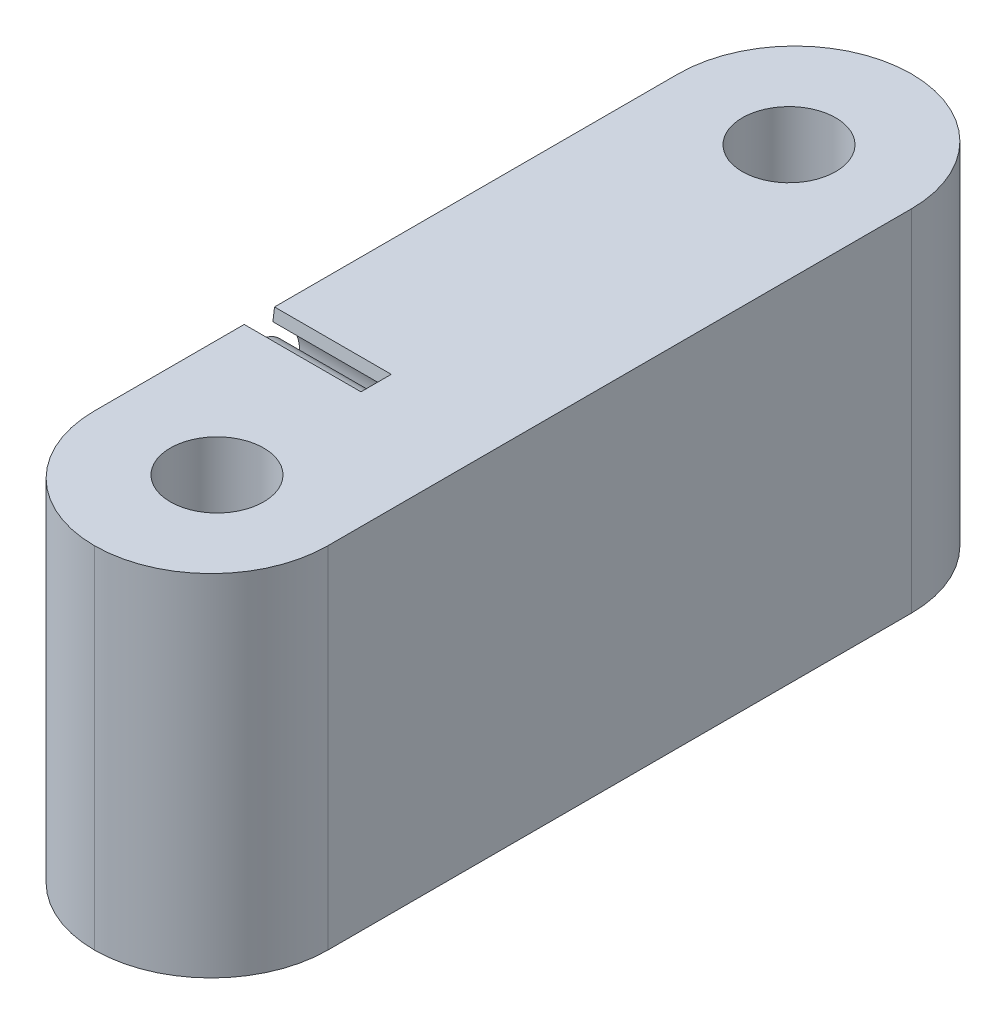
SolidWorks part; units mm, degrees
ref_plane "Front Plane" through (0, 0, 0) normal (0, 0, 1) x (1, 0, 0)
ref_plane "Top Plane" through (0, 0, 0) normal (0, 1, 0) x (1, 0, 0)
ref_plane "Right Plane" through (0, 0, 0) normal (1, 0, 0) x (0, 0, -1)
sketch "Sketch2" plane through (0, 0, 0) normal (0, 1, 0) x (1, 0, 0)
  line L1 (-3.5224, 29.7612) -> (16.4776, 29.7612)
  line L2 (-3.5224, 29.7612) -> (-3.5224, -40.2388)
  line L3 (-3.5224, -40.2388) -> (16.4776, -40.2388)
  line L4 (16.4776, 29.7612) -> (16.4776, -40.2388)
  dimension "D1" = 70
  dimension "D2" = 20
extrude "Boss-Extrude1" add sketch "Sketch2" along normal blind 30
sketch "Sketch3" plane through (0, 30, 0) normal (0, 1, 0) x (1, 0, 0)
  line L1 (-3.5224, -40.2388) -> (16.4776, -40.2388) construction
  line L3 (16.4776, -40.2388) -> (16.4776, 29.7612) construction
  line L4 (16.4776, 29.7612) -> (-3.5224, 29.7612) construction
  circle A0 centre (6.4776, 19.2612) radius 4
  circle A1 centre (6.4776, -29.7388) radius 4
  point P2 (0, 0)
  point P7 (0, 0)
  point P9 (-83.4642, 48.7576)
  dimension "D13" = 8
  dimension "D14" = 8
  dimension "D2" = 49
  dimension "D3" = 10.5
  dimension "D4" = 10.5
  dimension "D5" = 10
extrude "Cut-Extrude1" cut sketch "Sketch3" against normal blind 20
sketch "Sketch4" plane through (-3.5224, 0, 0) normal (-1, 0, 0) x (0, 0, 1)
  line L0 (8.1636, 30.0512) -> (8.1636, 15.6029) construction
  line L1 (-23.743, 30.1264) -> (40.1453, 30.1264)
  line L2 (-23.743, 30.1264) -> (-23.743, 15.6782)
  line L3 (-23.743, 15.6782) -> (40.1453, 15.6782)
  line L4 (40.1453, 30.1264) -> (40.1453, 15.6782)
  line L5 (14.95, 28.9694) -> (14.7857, 30.2017)
  line L6 (14.7857, 30.2017) -> (17.4195, 30.2017)
  line L7 (17.4195, 30.2017) -> (17.3442, 28.9224)
  circle A0 centre (16.1636, 25.6866) radius 2.5
  circle A1 centre (16.1636, 25.6866) radius 3.5
  line M5 (40.2388, 30) -> (-29.7612, 30)
  dimension "D2" = 5
  dimension "D3" = 7
  dimension "D1" = 8
extrude "Cut-Extrude2" cut sketch "Sketch4" against normal blind 10 contours A1 L7 L5 M5 | A1 A0 region at (-3.5224, 29.5608, 16.1236) region at (-3.5224, 29.0876, 16.1483)
fillet "Fillet1" radius 10 4 edges at (-3.5224, 15, -29.7612) (16.4776, 15, -29.7612) (16.4776, 15, 40.2388) (-3.5224, 15, 40.2388)
